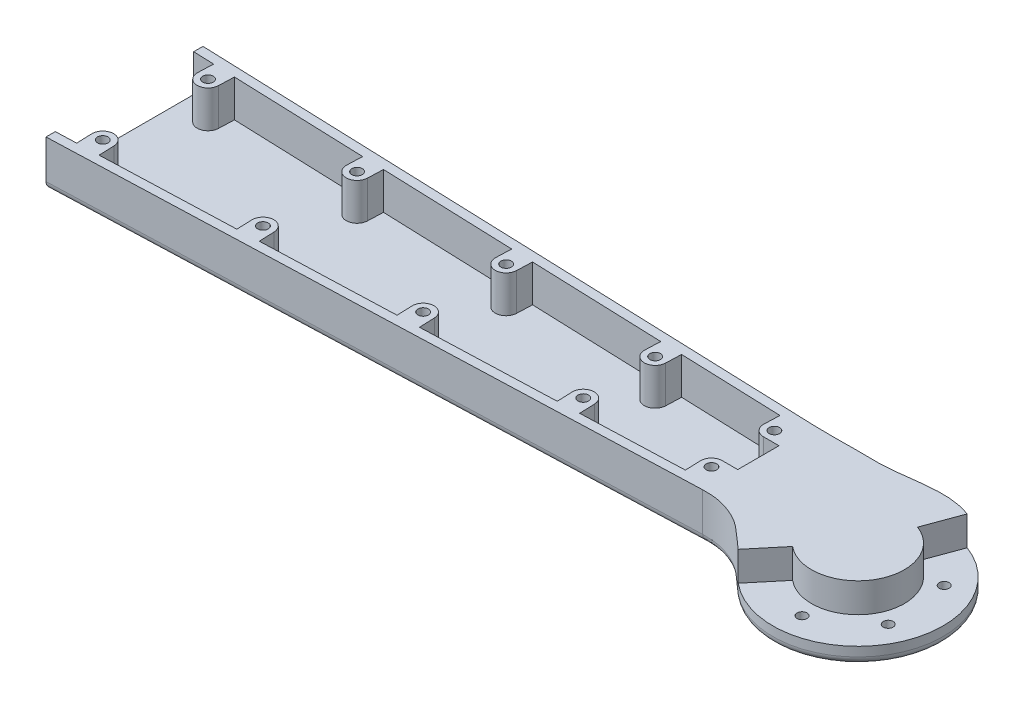
SolidWorks part; units mm, degrees
material "Thornel Mat VMA"
ref_plane "Front Plane" through (0, 0, 0) normal (0, 0, 1) x (1, 0, 0)
ref_plane "Top Plane" through (0, 0, 0) normal (0, 1, 0) x (1, 0, 0)
ref_plane "Right Plane" through (0, 0, 0) normal (1, 0, 0) x (0, 0, -1)
sketch "Sketch1" plane through (0, 0, 0) normal (0, 1, 0) x (1, 0, 0)
  line L0 (-40, 25.38) -> (165, 18)
  line L1 (-40, -25.38) -> (165, -18)
  line L2 (-40, 25.38) -> (-40, -25.38)
  line L3 (165, 18) -> (165, -18)
  line L4 (-85, 0) -> (165, 0) construction
  line L5 (-40, 25.38) -> (-85, 27)
  line L6 (-85, 27) -> (-85, -27)
  line L7 (-85, -27) -> (-40, -25.38)
  line L8 (73.6776, 18.2857) -> (165, 14.9981)
  line L9 (-85, -23.9981) -> (165, -14.9981)
  line L10 (-33.3179, 22.1375) -> (-33.4977, 17.1407)
  line L11 (-26.3224, 21.8857) -> (-26.5023, 16.8889)
  line L12 (16.6821, 20.3375) -> (16.5023, 15.3407)
  line L13 (23.6776, 20.0857) -> (23.4977, 15.0889)
  line L14 (66.6821, 18.5375) -> (66.5023, 13.5407)
  line L15 (73.6776, 18.2857) -> (73.4977, 13.2889)
  line L16 (73.6776, 18.2857) -> (-85, 23.9981)
  line L17 (205, -7.8003) -> (181.1843, 5.9497) construction
  line L18 (156.6821, 15.2975) -> (156.5023, 10.3007)
  line L19 (165, 6.6748) -> (160, 6.6748)
  line L20 (165, 18) -> (214.5182, 18) construction
  line L21 (214.5182, 18) -> (205, -7.8003)
  line L22 (165, -6.6748) -> (160, -6.6748)
  line L23 (156.6821, -15.2975) -> (156.5023, -10.3007)
  line L24 (73.6776, -18.2857) -> (73.4977, -13.2889)
  line L25 (66.6821, -18.5375) -> (66.5023, -13.5407)
  line L26 (23.6776, -20.0857) -> (23.4977, -15.0889)
  line L27 (16.6821, -20.3375) -> (16.5023, -15.3407)
  line L28 (-26.3224, -21.8857) -> (-26.5023, -16.8889)
  line L29 (-33.3179, -22.1375) -> (-33.4977, -17.1407)
  line L30 (205, -7.8003) -> (187.4154, -28.9434)
  line L31 (165, -18) -> (211.517, -18) construction
  line L32 (116.6821, 16.7375) -> (116.5023, 11.7407)
  line L33 (177.5, -7.8003) -> (205, -7.8003) construction
  line L35 (123.6776, 16.4857) -> (123.4977, 11.4889)
  line L36 (123.6776, -16.4857) -> (123.4977, -11.4889)
  line L37 (116.6821, -16.7375) -> (116.5023, -11.7407)
  arc A0 (-33.4977, 17.1407) -> (-26.5023, 16.8889) centre (-30, 17.0148) ccw
  circle A1 centre (-30, 17.0148) radius 1.7
  circle A2 centre (-30, 17.0148) radius 3
  arc A3 (16.5023, 15.3407) -> (23.4977, 15.0889) centre (20, 15.2148) ccw
  circle A4 centre (20, 15.2148) radius 1.7
  circle A5 centre (20, 15.2148) radius 3
  arc A6 (66.5023, 13.5407) -> (73.4977, 13.2889) centre (70, 13.4148) ccw
  circle A7 centre (70, 13.4148) radius 1.7
  circle A8 centre (70, 13.4148) radius 3
  arc A9 (156.5023, 10.3007) -> (160, 6.6748) centre (160, 10.1748) ccw
  circle A10 centre (160, 10.1748) radius 1.7
  arc A11 (156.5023, -10.3007) -> (160, -6.6748) centre (160, -10.1748) cw
  circle A12 centre (160, -10.1748) radius 1.7
  circle A13 centre (70, -13.4148) radius 1.7
  circle A14 centre (70, -13.4148) radius 3
  arc A15 (66.5023, -13.5407) -> (73.4977, -13.2889) centre (70, -13.4148) cw
  circle A16 centre (20, -15.2148) radius 1.7
  circle A17 centre (20, -15.2148) radius 3
  arc A18 (16.5023, -15.3407) -> (23.4977, -15.0889) centre (20, -15.2148) cw
  circle A19 centre (-30, -17.0148) radius 1.7
  circle A20 centre (-30, -17.0148) radius 3
  arc A21 (-33.4977, -17.1407) -> (-26.5023, -16.8889) centre (-30, -17.0148) cw
  circle A22 centre (160, 10.1748) radius 3
  circle A23 centre (160, -10.1748) radius 3
  circle A28 centre (205, -7.8003) radius 20 construction
  circle A29 centre (205, -7.8003) radius 27.5
  arc A30 (195.4084, -19.3329) -> (210.1918, 6.2726) centre (205, -7.8003) ccw
  circle A31 centre (206.83, -27.7164) radius 1.6 construction
  circle A32 centre (223.1629, -16.1735) radius 1.6 construction
  circle A33 centre (221.3328, 3.7426) radius 1.6 construction
  circle A34 centre (206.83, -27.7164) radius 1.6
  circle A35 centre (223.1629, -16.1735) radius 1.6
  circle A36 centre (221.3328, 3.7426) radius 1.6
  arc A37 (116.5023, 11.7407) -> (123.4977, 11.4889) centre (120, 11.6148) ccw
  circle A38 centre (120, 11.6148) radius 1.7
  circle A39 centre (120, 11.6148) radius 3
  arc A40 (116.5023, -11.7407) -> (123.4977, -11.4889) centre (120, -11.6148) cw
  circle A41 centre (120, -11.6148) radius 1.7
  circle A42 centre (120, -11.6148) radius 3
  spline S2 degree 3 poles (165, 18) (170.6874, 17.7953) (176.0608, 18.1889) (193.7614, 17.3942) (205.3096, 21.3972) (214.5182, 18) knots 0 0 0 0 0.252432 0.452763 1 1 1 1
  spline S3 degree 3 poles (165, -18) (166.6015, -17.9423) (171.4511, -18.1646) (180.0209, -21.6181) (183.7268, -25.8756) (187.4154, -28.9434) knots 0 0 0 0 0.193015 0.557683 1 1 1 1
  dimension "D13" = 3.4
  dimension "D14" = 6
  dimension "D15" = 3.4
  dimension "D16" = 6
  dimension "D21" = 3.4
  dimension "D22" = 6
  dimension "D24" = 3.4
  dimension "D25" = 6
  dimension "D30" = 50
  dimension "D32" = 50.25
  dimension "D34" = 4.95
  dimension "D36" = 13.7
  dimension "D33" = 40
  dimension "D23" = 55
  dimension "D38" = 10.5
  dimension "D44" = 15
  dimension "D47" = 6
  dimension "D48" = 3.4
  dimension "D2" = 54
  dimension "D3" = 36
  dimension "D4" = 5
  dimension "D5" = 5
  dimension "D6" = 7
  dimension "D7" = 5
  dimension "D8" = 5
  dimension "D9" = 7
  dimension "D10" = 5
  dimension "D11" = 5
  dimension "D12" = 7
  dimension "D17" = 50
  dimension "D18" = 10
  dimension "D19" = 5
  dimension "D20" = 3.5
  dimension "D26" = 205
  dimension "D27" = 3
  dimension "D28" = 45
  dimension "D29" = 0
  dimension "D31" = 3
  dimension "D35" = 80.25
  dimension "D37" = 30
  dimension "D39" = 13.85
  dimension "D40" = 40
  dimension "D41" = 12.5
  dimension "D42" = 22.5
  dimension "D43" = 5
  dimension "D45" = 7
  dimension "D46" = 5
  dimension "D49" = 50
  dimension "D50" = 40
extrude "Boss-Extrude1" add sketch "Sketch1" along normal blind 15 contours L16 L8 L3 L0 L2 | L9 L2 L1 L3 | L10 A0 L11 L16 A2 | A21 L29 L9 L28 A20 | A18 L27 L9 L26 A17 | L12 A3 L13 L16 A5 | L14 A6 L15 L16 A8 | A15 L25 L9 L24 A14 | A11 L23 L9 L3 L22 A23 | L18 A9 L19 L3 L8 A22 | L32 A37 L35 L8 A39 | A40 L37 L9 L36 A42 region at (62.5, 0, -20.189) region at (164.8789, 0, -10.8364) region at (62.5, 0, 20.189) region at (-29.8242, 0, -21.8995) region at (-33.2957, 0, 19.6351) region at (164.8789, 0, 10.8364) region at (123.4756, 0, -13.9913) region at (20.1758, 0, -20.0995) region at (16.7043, 0, 17.8351) region at (73.4756, 0, -15.7913) region at (120.1758, 0, 16.4995) region at (66.7043, 0, 16.0351)
extrude "Boss-Extrude2" add sketch "Sketch1<3>" along normal blind 3 contours L2 L4 L3 L19 A9 L18 L8 L15 A6 L14 L16 L13 A3 L12 L11 A0 L10 | L4 L2 L9 L29 A21 L28 L27 A18 L26 L25 A15 L24 L23 A11 L22 L3 | L18 A9 L19 L3 L8 A22 | A11 L23 L9 L3 L22 A23 region at (54.3645, 0, 0) region at (164.8789, 0, -10.8364) region at (164.8789, 0, 10.8364)
sketch "Sketch1<3>" plane through (0, 0, 0) normal (0, 1, 0) x (1, 0, 0) same geometry as "Sketch1"
extrude "Boss-Extrude3" add sketch "Sketch1<6>" along normal blind 15 contours L3 | A29 L30 L21 | L30 A30 L21 region at (174.066, 0, -1.5737) region at (193.8214, 0, 1.3611) region at (209.9025, 0, 10.6307)
sketch "Sketch1<6>" plane through (0, 0, 0) normal (0, 1, 0) x (1, 0, 0) same geometry as "Sketch1"
extrude "Boss-Extrude4" add sketch "Sketch1<8>" along normal blind 5.5 contours A30 L30 A29 L21 region at (226.9883, 0, -7.5247)
sketch "Sketch1<8>" plane through (0, 0, 0) normal (0, 1, 0) x (1, 0, 0) same geometry as "Sketch1"
extrude "Boss-Extrude5" add sketch "Sketch1<9>" along normal up to surface (15 mm away) from offset 7.5 contours A22 A10 | A23 A12 | A8 A7 | A14 A13 | A5 A4 | A17 A16 | A20 A19 | A2 A1 | A39 A38 | A42 A41 region at (-32.9151, 0, -17.0148) region at (17.0849, 0, -15.2148) region at (67.0849, 0, -13.4148) region at (67.0849, 0, 13.4148) region at (17.0849, 0, 15.2148) region at (-32.9151, 0, 17.0148) region at (157.0849, 0, -10.1748) region at (157.0849, 0, 10.1748) region at (117.0849, 0, -11.6148) region at (117.0849, 0, 11.6148) up to face at (73.4691, 15, 0.546)
sketch "Sketch1<9>" plane through (0, 0, 0) normal (0, 1, 0) x (1, 0, 0) same geometry as "Sketch1"
fillet "Fillet1" radius 2.5 5 edges at (62.5, 0, 21.69) (62.5, 0, -21.69) (228.8157, 0, 21.5503)
